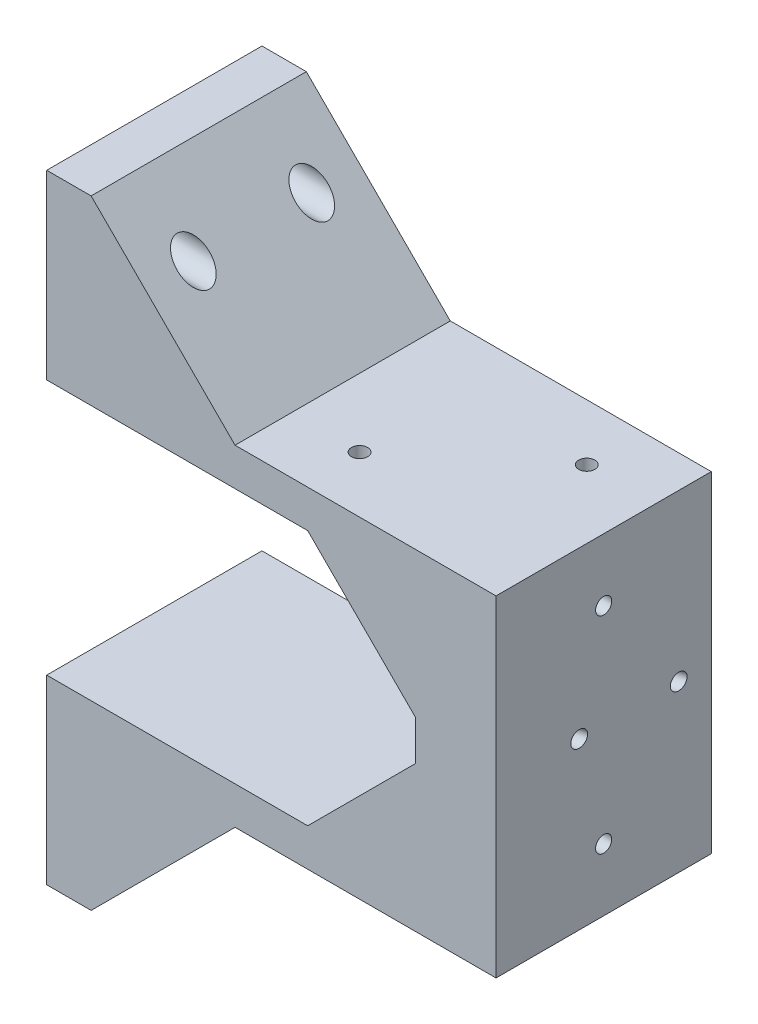
SolidWorks part; units mm, degrees
ref_plane "Top Plane" through (0, 0, 0) normal (0, 0, 1) x (1, 0, 0)
ref_plane "Right Plane" through (0, 0, 0) normal (0, 1, 0) x (1, 0, 0)
ref_plane "Front Plane" through (0, 0, 0) normal (1, 0, 0) x (0, 0, -1)
sketch "Sketch1" plane through (0, 0, 0) normal (0, 0, 1) x (1, 0, 0)
  line L0 (18.7122, 9.75) -> (30, 9.75) construction
  line L1 (10, 57.5) -> (15, 57.5)
  line L2 (10, 57.5) -> (10, 23.75)
  line L4 (15, 57.5) -> (15, 30.75)
  line L5 (10, 23.75) -> (78.5, 23.75)
  line L7 (15, 30.75) -> (93.5, 30.75)
  line L10 (78.5, 23.75) -> (78.5, 0)
  line L11 (78.5, 0) -> (93.5, 0)
  line L12 (93.5, 30.75) -> (93.5, 0)
  line L13 (0, 0) -> (78.5, 0) construction
  line L15 (53.5, 4.75) -> (53.5, -4.75) construction
  dimension "D1" = 14
  dimension "D2" = 7
  dimension "D3" = 5
  dimension "D4" = 15
  dimension "D5" = 25
extrude "Boss-Extrude1" add sketch "Sketch1" against normal blind 40
mirror "Mirror1" about plane through (78.5, 0, -40) normal (0, -1, 0) of "Boss-Extrude1"
chamfer "Chamfer1" distance 20 angle 45 2 edges at (78.5, 23.75, -20) (78.5, -23.75, -20)
chamfer "Chamfer2" distance 30 angle 45 2 edges at (15, 30.75, -20) (15, -30.75, -20)
ref_axis "Axis1" through (29.65, -5, -91.35) along (0, -1, 0)
ref_plane "Plane1" through (51.6014, 0, -14.7965) normal (0.9613, 0, -0.2756) x (0, -1, 0)
sketch "Sketch2" plane through (51.6014, 0, -14.7965) normal (0.9613, 0, -0.2756) x (0, -1, 0)
  circle A0 centre (0, -10.9183) radius 3.25
  circle A1 centre (0, 6.865) radius 3.25
  ellipse E0 centre (0, -10.9183) end of major axis (-3.25, -10.9183) minor radius 3.1241 construction
  ellipse E1 centre (0, 6.865) end of major axis (-3.25, 6.865) minor radius 3.1241 construction
  point P2 (0, -10.9183)
  dimension "D1" = 6.5
extrude "Cut-Extrude1" cut sketch "Sketch2" along normal blind 32 contours A0
extrude "Cut-Extrude5" cut sketch "Sketch2<3>" along normal blind 32 from offset 5 contours A1 region at (49.7091, 0, -21.3955)
sketch "Sketch2<3>" plane through (51.6014, 0, -14.7965) normal (0.9613, 0, -0.2756) x (0, -1, 0) same geometry as "Sketch2"
sketch "Sketch5" plane through (93.5, 0, 0) normal (1, 0, 0) x (0, 0, -1)
  circle A0 centre (31, -47.5) radius 1.65 construction
  circle A1 centre (9, -47.5) radius 1.65 construction
  circle A2 centre (9, 47.5) radius 1.65 construction
  circle A3 centre (31, 47.5) radius 1.65 construction
  circle A4 centre (31, -47.5) radius 1.65
  circle A5 centre (9, -47.5) radius 1.65
  circle A6 centre (9, 47.5) radius 1.65
  circle A7 centre (31, 47.5) radius 1.65
extrude "Cut-Extrude2" cut sketch "Sketch5" against normal through all
sketch "Sketch6" plane through (93.5, 0, 0) normal (1, 0, 0) x (0, 0, -1)
  circle A0 centre (31, -47.5) radius 1.65 construction
  circle A1 centre (9, -47.5) radius 1.65 construction
  circle A2 centre (9, 47.5) radius 1.65 construction
  circle A3 centre (31, 47.5) radius 1.65 construction
  circle A4 centre (31, -47.5) radius 1.65 construction
  circle A5 centre (9, -47.5) radius 1.65 construction
  circle A6 centre (9, 47.5) radius 1.65 construction
  circle A7 centre (31, 47.5) radius 1.65 construction
  circle A8 centre (31, -47.5) radius 3
  circle A9 centre (9, -47.5) radius 3
  circle A10 centre (31, 47.5) radius 3
  circle A11 centre (9, 47.5) radius 3
  dimension "D1" = 6
extrude "Cut-Extrude3" cut sketch "Sketch6" against normal offset from surface (76.5 mm away) 7 up to face at (10, 47.5, -32.65)
sketch "Sketch7" plane through (93.5, 0, 0) normal (1, 0, 0) x (0, 0, -1)
  line L0 (108.25, -19.1667) -> (20, -19.1667) construction
  line L1 (20, -19.1667) -> (20, 19.1667) construction
  line L2 (20, 19.1667) -> (108.25, 19.1667) construction
  line L3 (40, 0) -> (0, 0) construction
  line L4 (40, -30.75) -> (40, 30.75) construction
  line L5 (0, -30.75) -> (0, 30.75) construction
  circle A0 centre (20, -19.1667) radius 1.5
  circle A1 centre (20, 19.1667) radius 1.5
  circle A2 centre (108.25, -19.1667) radius 1.5 construction
  point P16 (20, 0)
extrude "Cut-Extrude4" cut sketch "Sketch7" against normal blind 10
sketch "Sketch8" plane through (51.6014, 0, -14.7965) normal (0.9613, 0, -0.2756) x (0, -1, 0)
  circle A0 centre (0, -10.9183) radius 1.5
  circle A1 centre (0, 6.865) radius 1.5
  circle A2 centre (0, -10.9183) radius 3.25 construction
  circle A3 centre (0, 6.865) radius 3.25 construction
  dimension "D1" = 3
extrude "Cut-Extrude6" cut sketch "Sketch8" along normal through all
sketch "Sketch9" plane through (77.7135, 0, -13.703) normal (0.9848, 0, -0.1736) x (-0.1736, 0, -0.9848)
  line L1 (6.2509, 9.75) -> (26.8028, 9.75) construction
  line L2 (26.8028, 9.75) -> (26.8028, -9.75) construction
  line L3 (6.2509, 9.75) -> (4.8135, 9.75)
  line L4 (4.8135, -9.75) -> (14.8135, -9.75)
  line L5 (14.8135, -9.75) -> (14.8135, -4.949)
  line L6 (6.2509, 9.75) -> (4.8135, 9.75) construction
  line L7 (4.8135, -9.75) -> (14.8135, -9.75) construction
  line L9 (26.8028, -9.75) -> (14.8135, -9.75) construction
  line L11 (25.7609, 3.75) -> (29.2339, 23.75) construction
  line L13 (25.7609, 3.75) -> (29.2339, 23.75) construction
  line L14 (4.8135, -13.75) -> (14.8135, -13.75)
  line L15 (30.8028, -13.75) -> (14.8135, -13.75)
  line L16 (30.8028, 13.75) -> (30.8028, -13.75)
  line L17 (6.2509, 13.75) -> (30.8028, 13.75)
  line L18 (6.2509, 13.75) -> (4.8135, 13.75)
  arc A0 (4.8135, 13.75) -> (4.8135, -13.75) centre (4.8135, 0) ccw
  arc A2 (6.2509, 9.75) -> (8.9115, 3.1051) centre (31.1135, 15.85) ccw
  arc A3 (4.8135, 9.75) -> (4.8135, -9.75) centre (4.8135, 0) ccw
  arc A5 (4.8135, 9.75) -> (4.8135, -9.75) centre (4.8135, 0) ccw construction
  arc A39 (8.9115, 3.1051) -> (14.8135, -4.949) centre (13.1206, 0) ccw
  arc A40 (8.9115, 3.1051) -> (14.8135, -4.949) centre (13.1206, 0) ccw
  dimension "D2" = 4
  dimension "D1" = 0
extrude "Cut-Extrude7" cut sketch "Sketch9" against normal through all contours L14 L15 L16 L17 L18 A0
sketch "Sketch10" plane through (0, 30.75, 0) normal (0, 1, 0) x (1, 0, 0)
  line L0 (93.5, 40) -> (45, 0) construction
  line L1 (81.7765, 28.3868) -> (58.6323, 9.2988) construction
  line L2 (69.25, 20) -> (70.2044, 18.8428) construction
  circle A0 centre (80.8221, 29.544) radius 1.5
  circle A1 centre (57.6779, 10.456) radius 1.5
  dimension "D1" = 3
  dimension "D2" = 30
extrude "Cut-Extrude8" cut sketch "Sketch10" against normal blind 5
